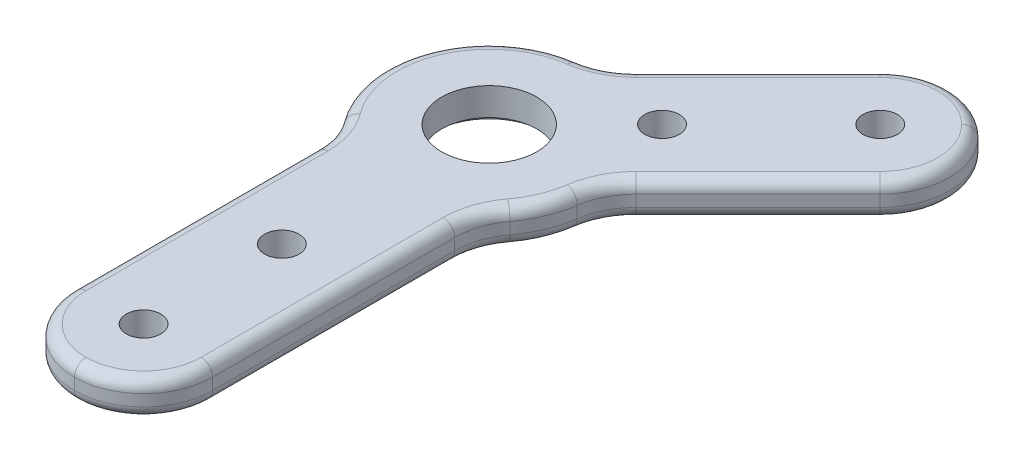
SolidWorks part; units mm, degrees
material "6061 Alloy"
ref_plane "Front Plane" through (0, 0, 0) normal (0, 0, 1) x (1, 0, 0)
ref_plane "Top Plane" through (0, 0, 0) normal (0, 1, 0) x (1, 0, 0)
ref_plane "Right Plane" through (0, 0, 0) normal (1, 0, 0) x (0, 0, -1)
sketch "Sketch1" plane through (0, 0, 0) normal (0, 1, 0) x (1, 0, 0)
  line L0 (0, 44.45) -> (0, -44.45) construction
  line L1 (-12.7, -44.45) -> (12.7, -44.45)
  line L2 (-12.7, -44.45) -> (-12.7, 31.75)
  line L3 (-12.7, 44.45) -> (12.7, 44.45) construction
  line L4 (12.7, -44.45) -> (12.7, 31.75)
  line L5 (-12.7, -44.45) -> (12.7, 44.45) construction
  line L6 (-12.7, 44.45) -> (12.7, -44.45) construction
  line L7 (0, 31.75) -> (44.9013, 76.6513) construction
  line L8 (8.9803, 22.7697) -> (53.8815, 67.671)
  line L9 (53.8815, 67.671) -> (35.921, 85.6315)
  line L10 (35.921, 85.6315) -> (-8.9803, 40.7303)
  line L11 (-8.9803, 40.7303) -> (8.9803, 22.7697) construction
  line L12 (12.7, 44.45) -> (12.7, 31.75) construction
  line L13 (53.8815, 67.671) -> (53.8815, -44.45) construction
  line L14 (53.8815, -44.45) -> (12.7, -44.45) construction
  line L15 (12.7, 44.45) -> (12.7, 62.4105) construction
  circle A0 centre (0, 31.75) radius 12.7 construction
  circle A1 centre (0, -31.75) radius 3.175
  circle A2 centre (0, -6.35) radius 3.175
  circle A3 centre (0, 31.75) radius 8.7312
  circle A4 centre (35.921, 67.671) radius 3.175
  circle A5 centre (15.875, 47.625) radius 3.175
  circle A6 centre (0, 31.75) radius 19.05
  point P0 (0, 0)
  point P16 (44.9013, 76.6513)
  point P21 (0, 31.75)
  dimension "D4" = 12.7
  dimension "D1" = 6.35
  dimension "D7" = 50.8
  dimension "D8" = 12.7
  dimension "D9" = 17.4625
  dimension "D10" = 6.35
  dimension "D2" = 25.4
  dimension "D3" = 45
  dimension "D5" = 25.4
  dimension "D6" = 38.1
extrude "Boss-Extrude1" add sketch "Sketch1" along normal blind 6.35 contours A0 L2 L1 L4 L8 A2 A1 | A0 L4 L8 L9 L10 A4 | A0 L8 L4 | L4 A6 L8 region at (0, 0, 14.9202) region at (-17.1023, 0, -38.834) region at (15.553, 0, -25.3078) region at (28.7883, 0, -60.5383)
fillet "Fillet2" radius 12.7 8 edges at (35.921, 3.175, -85.6315) (53.8815, 3.175, -67.671) (-12.7, 3.175, 44.45) (12.7, 3.175, 44.45) (12.7, 3.175, -17.551) (19.0205, 3.175, -32.81) (1.06, 3.175, -50.7705) (-12.7, 3.175, -17.551)
fillet "Fillet3" radius 2.1167 28 edges at (12.7, 0, 9.525) (8.9803, 0, 40.7303) (-8.9803, 0, 40.7303) (-12.7, 0, 9.525) (15.7154, 0, -65.426) (35.921, 0, -80.371) (48.621, 0, -67.671) (12.7, 6.35, 9.525) (8.9803, 6.35, 40.7303) (-8.9803, 6.35, 40.7303) (-12.7, 6.35, 9.525) (15.7154, 6.35, -65.426) (35.921, 6.35, -80.371) (48.621, 6.35, -67.671) (33.676, 0, -47.4654) (33.676, 6.35, -47.4654) (20.0717, 0, -32.9395) (17.5999, 0, -24.4599) (13.3517, 0, -16.7161) (-13.3517, 0, -16.7161) (-17.5999, 0, -39.0401) (1.1895, 0, -51.8217) (20.0717, 6.35, -32.9395) (17.5999, 6.35, -24.4599) (13.3517, 6.35, -16.7161) (-13.3517, 6.35, -16.7161) (-17.5999, 6.35, -39.0401) (1.1895, 6.35, -51.8217)
sketch "Sketch3" plane through (0, 0, 0) normal (0, -1, 0) x (1, 0, 0)
  circle A0 centre (0, -31.75) radius 10.2489
  dimension "D1" = 20.4978
extrude "Cut-Extrude1" cut sketch "Sketch3" against normal blind 1.27
